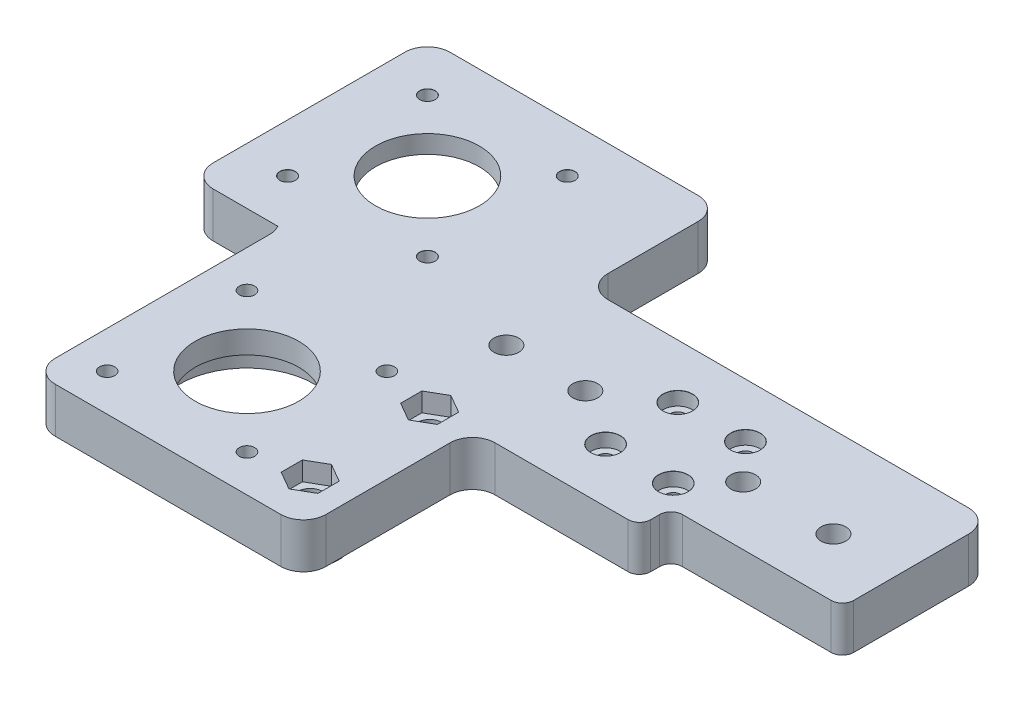
SolidWorks part; units mm, degrees
ref_plane "Front Plane" through (0, 0, 0) normal (0, 0, 1) x (1, 0, 0)
ref_plane "Top Plane" through (0, 0, 0) normal (0, 1, 0) x (1, 0, 0)
ref_plane "Right Plane" through (0, 0, 0) normal (1, 0, 0) x (0, 0, -1)
sketch "Sketch1" plane through (0, 0, 0) normal (0, 1, 0) x (1, 0, 0)
  line L0 (0, 0) -> (110, 0) construction
  line L1 (110, 0) -> (110, 20) construction
  line L2 (110, 20) -> (0, 20) construction
  line L3 (0, 20) -> (0, 0) construction
  line L4 (110, 30) -> (110, -10) construction
  line L5 (110, 30) -> (80, 30) construction
  line L6 (80, 30) -> (80, -10) construction
  line L7 (80, -10) -> (110, -10) construction
  line L8 (0, 67.5) -> (0, -47.5)
  line L16 (0, 67.5) -> (60, 67.5)
  line L18 (0, -47.5) -> (60, -47.5)
  line L19 (60, 67.5) -> (60, 30)
  line L22 (110, -10) -> (60, -10)
  line L23 (60, -10) -> (60, -47.5)
  line L24 (60, 30) -> (110, 30)
  line L25 (110, 30) -> (110, -10)
  point P8 (110, 10)
  point P13 (0, 10)
  dimension "D1" = 20
  dimension "D2" = 37.5
  dimension "D3" = 30
  dimension "D4" = 40
  dimension "D5" = 110
  dimension "D6" = 20
extrude "Boss-Extrude1" add sketch "Sketch1" along normal blind 10
fillet "Fillet1" radius 5 7 edges at (60, 5, -30) (110, 5, -30) (110, 5, 10) (0, 5, 47.5) (0, 5, -67.5) (60, 5, -67.5) (60, 5, 47.5)
sketch "Sketch3" plane through (0, 10, 0) normal (0, 1, 0) x (1, 0, 0)
  line L0 (5, -47.5) -> (55, -47.5) construction
  line L1 (0, 62.5) -> (0, -42.5) construction
  circle A0 centre (23.75, -23.75) radius 11.5
  dimension "D3" = 23
  dimension "D1" = 23.75
  dimension "D2" = 23.75
extrude "Cut-Extrude1" cut sketch "Sketch3" against normal blind 10
sketch "Sketch4" plane through (0, 0, 0) normal (0, -1, 0) x (1, 0, 0)
  line L1 (39.25, 39.25) -> (8.25, 39.25)
  line L2 (39.25, 39.25) -> (39.25, 8.25)
  line L3 (39.25, 8.25) -> (8.25, 8.25)
  line L4 (8.25, 39.25) -> (8.25, 8.25)
  line L5 (39.25, 39.25) -> (8.25, 8.25) construction
  line L6 (39.25, 8.25) -> (8.25, 39.25) construction
  point P0 (23.75, 23.75)
  dimension "D1" = 31
hole_wizard "CBORE for M3 SHCS1" positions "Sketch5" profile "Sketch6" counterbore size "M3" standard "ANSI Metric" end condition through all
sketch "Sketch5" plane through (0, 0, 0) normal (0, -1, 0) x (-1, 0, 0)
  point P0 (-39.25, -8.25)
  point P3 (-8.25, -39.25)
  point P6 (-8.25, -8.25)
  point P9 (-39.25, -39.25)
sketch "Sketch6" plane through (39.25, 0, 8.25) normal (1, 0, 0) x (0, 0, -1)
  line L0 (0, 0) -> (0, 10)
  line L1 (0, 10) -> (1.7, 10)
  line L3 (1.7, 10) -> (1.7, 3)
  line L4 (3.25, 3) -> (1.7, 3)
  line L5 (3.25, 3) -> (3.25, 0.025)
  line L6 (3.25, 0.025) -> (3.275, 0)
  line L7 (3.275, 0) -> (0, 0)
  line L8 (-3.25, 0.025) -> (-3.275, 0) construction
  line L11 (0, -6.35) -> (0, 107.95) construction
  dimension "Thru Hole Dia." = 3.4
  dimension "Thru Hole Depth" = 10
  dimension "C'Bore Dia." = 6.5
  dimension "C'Bore Depth" = 3
  dimension "Near C'Sink Dia." = 6.55
  dimension "Near C'Sink Angle" = 90
sketch "Sketch7" plane through (0, 10, 0) normal (0, 1, 0) x (1, 0, 0)
  line L1 (92.5, 18) -> (77.5, 18)
  line L2 (92.5, 18) -> (92.5, 2)
  line L3 (92.5, 2) -> (77.5, 2)
  line L4 (77.5, 18) -> (77.5, 2)
  line L5 (92.5, 18) -> (77.5, 2) construction
  line L6 (92.5, 2) -> (77.5, 18) construction
  line L7 (110, 10) -> (0, 10)
  line L8 (0, 67.5) -> (0, -47.5) construction
  line L10 (110, 30) -> (110, -10) construction
  point P0 (85, 10)
  dimension "D1" = 15
  dimension "D2" = 16
  dimension "D3" = 25
hole_wizard "CBORE for M3 SHCS2" positions "Sketch8" profile "Sketch9" counterbore size "M3" standard "ANSI Metric" end condition through all
sketch "Sketch8" plane through (0, 10, 0) normal (0, 1, 0) x (1, 0, 0)
  point P0 (77.5, 18)
  point P3 (92.5, 18)
  point P6 (92.5, 2)
  point P9 (77.5, 2)
sketch "Sketch9" plane through (77.5, 10, -18) normal (1, 0, 0) x (0, 0, 1)
  line L0 (0, 0) -> (0, 10)
  line L1 (0, 10) -> (1.7, 10)
  line L3 (1.7, 10) -> (1.7, 3)
  line L4 (3.25, 3) -> (1.7, 3)
  line L5 (3.25, 3) -> (3.25, 0.025)
  line L6 (3.25, 0.025) -> (3.275, 0)
  line L7 (3.275, 0) -> (0, 0)
  line L8 (-3.25, 0.025) -> (-3.275, 0) construction
  line L11 (0, -6.35) -> (0, 107.95) construction
  dimension "Thru Hole Dia." = 3.4
  dimension "Thru Hole Depth" = 10
  dimension "C'Bore Dia." = 6.5
  dimension "C'Bore Depth" = 3
  dimension "Near C'Sink Dia." = 6.55
  dimension "Near C'Sink Angle" = 90
sketch "Sketch10" plane through (0, 0, 0) normal (0, -1, 0) x (1, 0, 0)
  line L0 (110, -10) -> (0, -10) construction
  line L1 (110, 5) -> (110, -25) construction
  line L2 (0, -62.5) -> (0, 42.5) construction
  point P6 (100, -10)
  point P7 (30, -10)
  point P8 (47.5, -10)
  point P9 (65, -10)
  dimension "D1" = 30
  dimension "D2" = 17.5
  dimension "D3" = 17.5
  dimension "D4" = 10
hole_wizard "CBORE for M5 SHCS1" positions "Sketch13" profile "Sketch12" counterbore size "M5" standard "ANSI Metric" end condition through all
sketch "Sketch13" plane through (0, 0, 0) normal (0, -1, 0) x (-1, 0, 0)
  point P0 (-100, 10)
  point P3 (-65, 10)
  point P6 (-47.5, 10)
sketch "Sketch12" plane through (100, 0, -10) normal (1, 0, 0) x (0, 0, -1)
  line L0 (0, 0) -> (0, 10)
  line L1 (0, 10) -> (2.75, 10)
  line L3 (2.75, 10) -> (2.75, 5)
  line L4 (5, 5) -> (2.75, 5)
  line L5 (5, 5) -> (5, 0.025)
  line L6 (5, 0.025) -> (5.025, 0)
  line L7 (5.025, 0) -> (0, 0)
  line L8 (-5, 0.025) -> (-5.025, 0) construction
  line L11 (0, -6.35) -> (0, 107.95) construction
  dimension "Thru Hole Dia." = 5.5
  dimension "Thru Hole Depth" = 10
  dimension "C'Bore Dia." = 10
  dimension "C'Bore Depth" = 5
  dimension "Near C'Sink Dia." = 10.05
  dimension "Near C'Sink Angle" = 90
sketch "Sketch14" plane through (0, 10, 0) normal (0, 1, 0) x (1, 0, 0)
  line L0 (0, 10) -> (-17.5, 10)
  line L1 (0, 62.5) -> (0, -42.5) construction
  line L2 (-17.5, 10) -> (-17.5, 67.5)
  line L3 (-17.5, 67.5) -> (5, 67.5)
  line L4 (0, 62.5) -> (0, 10)
  arc A0 (5, 67.5) -> (0, 62.5) centre (5, 62.5) ccw construction
  arc A1 (5, 67.5) -> (0, 62.5) centre (5, 62.5) ccw
  dimension "D1" = 17.5
extrude "Boss-Extrude2" add sketch "Sketch14" against normal blind 10
sketch "Sketch15" plane through (0, 10, 0) normal (0, 1, 0) x (1, 0, 0)
  line L0 (-17.5, 67.5) -> (55, 67.5)
  line L1 (-17.5, 67.5) -> (-17.5, 57.5)
  line L2 (-17.5, 67.5) -> (-17.5, 10) construction
  line L3 (-17.5, 57.5) -> (60, 57.5)
  line L5 (60, 35) -> (60, 62.5) construction
  line L6 (60, 57.5) -> (60, 62.5)
  arc A2 (60, 62.5) -> (55, 67.5) centre (55, 62.5) ccw construction
  arc A3 (60, 62.5) -> (55, 67.5) centre (55, 62.5) ccw
  dimension "D1" = 10
extrude "Cut-Extrude2" cut sketch "Sketch15" against normal blind 10
fillet "Fillet2" radius 5 4 edges at (0, 5, -10) (60, 5, -57.5) (-17.5, 5, -57.5) (-17.5, 5, -10)
sketch "Sketch16" plane through (0, 10, 0) normal (0, 1, 0) x (1, 0, 0)
  line L0 (-12.5, 57.5) -> (55, 57.5) construction
  line L1 (-17.5, 52.5) -> (-17.5, 15) construction
  circle A0 centre (6.25, 33.75) radius 11.5
  dimension "D1" = 23
  dimension "D2" = 23.75
  dimension "D3" = 23.75
extrude "Cut-Extrude3" cut sketch "Sketch16" against normal through all
sketch "Sketch17" plane through (0, 10, 0) normal (0, 1, 0) x (1, 0, 0)
  line L1 (21.75, 49.25) -> (-9.25, 49.25)
  line L2 (21.75, 49.25) -> (21.75, 18.25)
  line L3 (21.75, 18.25) -> (-9.25, 18.25)
  line L4 (-9.25, 49.25) -> (-9.25, 18.25)
  line L5 (21.75, 49.25) -> (-9.25, 18.25) construction
  line L6 (21.75, 18.25) -> (-9.25, 49.25) construction
  point P0 (6.25, 33.75)
  dimension "D1" = 31
hole_wizard "M3 Clearance Hole1" positions "Sketch18" profile "Sketch19" hole size "M3" standard "ANSI Metric" end condition through all
sketch "Sketch18" plane through (0, 10, 0) normal (0, 1, 0) x (1, 0, 0)
  point P0 (-9.25, 49.25)
  point P3 (21.75, 49.25)
  point P6 (21.75, 18.25)
  point P9 (-9.25, 18.25)
sketch "Sketch19" plane through (-9.25, 10, -49.25) normal (1, 0, 0) x (0, 0, 1)
  line L0 (0, 0) -> (0, 10)
  line L1 (0, 10) -> (1.7, 10)
  line L2 (1.7, 10) -> (1.7, 0.025)
  line L3 (1.7, 0.025) -> (1.725, 0)
  line L5 (1.725, 0) -> (0, 0)
  line L6 (-1.7, 0.025) -> (-1.725, 0) construction
  line L11 (0, -6.35) -> (0, 107.95) construction
  dimension "Thru Hole Dia." = 3.4
  dimension "Thru Hole Depth" = 10
  dimension "Near C'Sink Dia." = 3.45
  dimension "Near C'Sink Angle" = 90
sketch "Sketch20" plane through (0, 10, 0) normal (0, 1, 0) x (1, 0, 0)
  line L0 (23.75, -23.75) -> (60, -23.75) construction
  line L1 (60, -42.5) -> (60, -10) construction
  line L2 (51, -10.51) -> (51, -36.99) construction
  line L4 (55.075, -8.1573) -> (51, -5.8046)
  line L5 (51, -5.8046) -> (46.925, -8.1573)
  line L6 (46.925, -8.1573) -> (46.925, -12.8627)
  line L7 (46.925, -12.8627) -> (51, -15.2154)
  line L8 (51, -15.2154) -> (55.075, -12.8627)
  line L9 (55.075, -12.8627) -> (55.075, -8.1573)
  line L10 (51, -32.2846) -> (46.925, -34.6373)
  line L11 (46.925, -34.6373) -> (46.925, -39.3427)
  line L12 (46.925, -39.3427) -> (51, -41.6954)
  line L13 (51, -41.6954) -> (55.075, -39.3427)
  line L14 (55.075, -39.3427) -> (55.075, -34.6373)
  line L15 (55.075, -34.6373) -> (51, -32.2846)
  line L18 (0, 5) -> (0, -42.5) construction
  circle A0 centre (51, -10.51) radius 4.075 construction
  circle A1 centre (51, -36.99) radius 4.075 construction
  point P8 (51, -23.75)
  point P25 (51, -36.99)
  point P26 (51, -10.51)
  dimension "D1" = 26.48
  dimension "D2" = 9
  dimension "D3" = 8.15
extrude "Cut-Extrude4" cut sketch "Sketch20" against normal blind 4.2
hole_wizard "M5 Clearance Hole1" positions "Sketch22" profile "Sketch23" hole size "M5" standard "ANSI Metric" end condition through all
sketch "Sketch22" plane through (0, 10, 0) normal (0, 1, 0) x (1, 0, 0)
  point P0 (51, -10.51)
  point P3 (51, -36.99)
sketch "Sketch23" plane through (51, 10, 10.51) normal (1, 0, 0) x (0, 0, 1)
  line L0 (0, 0) -> (0, 10)
  line L1 (0, 10) -> (2.75, 10)
  line L2 (2.75, 10) -> (2.75, 0.025)
  line L3 (2.75, 0.025) -> (2.775, 0)
  line L5 (2.775, 0) -> (0, 0)
  line L6 (-2.75, 0.025) -> (-2.775, 0) construction
  line L11 (0, -6.35) -> (0, 107.95) construction
  dimension "Thru Hole Dia." = 5.5
  dimension "Thru Hole Depth" = 10
  dimension "Near C'Sink Dia." = 5.55
  dimension "Near C'Sink Angle" = 90
sketch "Sketch25" plane through (0, 0, 0) normal (0, -1, 0) x (1, 0, 0)
  circle A0 centre (23.75, 23.75) radius 15
  dimension "D1" = 30
extrude "Cut-Extrude6" cut sketch "Sketch25" against normal blind 5
sketch "Sketch26" plane through (0, 0, 0) normal (0, -1, 0) x (1, 0, 0)
  circle A0 centre (51, 36.99) radius 6.25
  circle A1 centre (51, 36.99) radius 2.75 construction
  circle A2 centre (51, 36.99) radius 2.75
  circle A3 centre (51, 10.51) radius 6.25
  circle A4 centre (51, 10.51) radius 2.75 construction
  circle A5 centre (51, 10.51) radius 2.75
  dimension "D1" = 12.5
extrude "Boss-Extrude3" add sketch "Sketch26" along normal blind 2.9
sketch "Sketch27" plane through (0, 10, 0) normal (0, 1, 0) x (1, 0, 0)
  line L0 (65, 30) -> (45, 30)
  line L1 (45, 30) -> (45, 57.5)
  line L2 (-12.5, 57.5) -> (55, 57.5) construction
  line L3 (45, 57.5) -> (55, 57.5)
  line L4 (60, 35) -> (60, 52.5) construction
  line L5 (60, 35) -> (60, 52.5)
  arc A0 (60, 35) -> (65, 30) centre (65, 35) ccw construction
  arc A1 (60, 52.5) -> (55, 57.5) centre (55, 52.5) ccw construction
  arc A2 (60, 35) -> (65, 30) centre (65, 35) ccw
  arc A3 (60, 52.5) -> (55, 57.5) centre (55, 52.5) ccw
  dimension "D1" = 15
extrude "Cut-Extrude7" cut sketch "Sketch27" against normal blind 10
fillet "Fillet3" radius 5 3 edges at (45, 5, -57.5) (45, 5, -30) (60, 5, 10)
sketch "Sketch31" plane through (0, 10, 0) normal (0, 1, 0) x (1, 0, 0)
  line L0 (-10.5429, 54.2071) -> (-14.2071, 50.5429) construction
  line L1 (22.3358, 54.5) -> (-9.8358, 54.5) construction
  line L2 (26.7071, 50.5429) -> (23.0429, 54.2071) construction
  line L3 (27, 17.6642) -> (27, 49.8358) construction
  line L4 (23.0429, 13.2929) -> (26.7071, 16.9571) construction
  line L5 (-9.8358, 13) -> (22.3358, 13) construction
  line L6 (-14.2071, 16.9571) -> (-10.5429, 13.2929) construction
  line L7 (-14.5, 49.8358) -> (-14.5, 17.6642) construction
  line L8 (-10.5429, 54.2071) -> (-14.2071, 50.5429) construction
  line L9 (22.3358, 54.5) -> (-9.8358, 54.5) construction
  line L10 (-15.5, 49.8358) -> (-15.5, 17.6642)
  line L11 (-14.9142, 16.25) -> (-11.25, 12.5858)
  line L12 (-9.8358, 12) -> (22.3358, 12)
  line L13 (23.75, 12.5858) -> (27.4142, 16.25)
  line L14 (28, 17.6642) -> (28, 49.8358)
  line L15 (27.4142, 51.25) -> (23.75, 54.9142)
  line L16 (22.3358, 55.5) -> (-9.8358, 55.5)
  line L17 (-11.25, 54.9142) -> (-14.9142, 51.25)
  line L30 (26.7071, 50.5429) -> (23.0429, 54.2071) construction
  line L31 (27, 17.6642) -> (27, 49.8358) construction
  line L32 (23.0429, 13.2929) -> (26.7071, 16.9571) construction
  line L33 (-9.8358, 13) -> (22.3358, 13) construction
  line L34 (-14.2071, 16.9571) -> (-10.5429, 13.2929) construction
  line L35 (-14.5, 49.8358) -> (-14.5, 17.6642) construction
  arc A0 (-14.2071, 50.5429) -> (-14.5, 49.8358) centre (-13.5, 49.8358) ccw construction
  arc A1 (-9.8358, 54.5) -> (-10.5429, 54.2071) centre (-9.8358, 53.5) ccw construction
  arc A2 (23.0429, 54.2071) -> (22.3358, 54.5) centre (22.3358, 53.5) ccw construction
  arc A3 (27, 49.8358) -> (26.7071, 50.5429) centre (26, 49.8358) ccw construction
  arc A4 (26.7071, 16.9571) -> (27, 17.6642) centre (26, 17.6642) ccw construction
  arc A5 (22.3358, 13) -> (23.0429, 13.2929) centre (22.3358, 14) ccw construction
  arc A6 (-10.5429, 13.2929) -> (-9.8358, 13) centre (-9.8358, 14) ccw construction
  arc A7 (-14.5, 17.6642) -> (-14.2071, 16.9571) centre (-13.5, 17.6642) ccw construction
  arc A8 (-14.2071, 50.5429) -> (-14.5, 49.8358) centre (-13.5, 49.8358) ccw construction
  arc A9 (-14.9142, 51.25) -> (-15.5, 49.8358) centre (-13.5, 49.8358) ccw
  arc A10 (-15.5, 17.6642) -> (-14.9142, 16.25) centre (-13.5, 17.6642) ccw
  arc A11 (-11.25, 12.5858) -> (-9.8358, 12) centre (-9.8358, 14) ccw
  arc A12 (22.3358, 12) -> (23.75, 12.5858) centre (22.3358, 14) ccw
  arc A14 (27.4142, 16.25) -> (28, 17.6642) centre (26, 17.6642) ccw
  arc A15 (28, 49.8358) -> (27.4142, 51.25) centre (26, 49.8358) ccw
  arc A17 (23.75, 54.9142) -> (22.3358, 55.5) centre (22.3358, 53.5) ccw
  arc A27 (-9.8358, 54.5) -> (-10.5429, 54.2071) centre (-9.8358, 53.5) ccw construction
  arc A28 (23.0429, 54.2071) -> (22.3358, 54.5) centre (22.3358, 53.5) ccw construction
  arc A29 (27, 49.8358) -> (26.7071, 50.5429) centre (26, 49.8358) ccw construction
  arc A30 (26.7071, 16.9571) -> (27, 17.6642) centre (26, 17.6642) ccw construction
  arc A31 (22.3358, 13) -> (23.0429, 13.2929) centre (22.3358, 14) ccw construction
  arc A32 (-10.5429, 13.2929) -> (-9.8358, 13) centre (-9.8358, 14) ccw construction
  arc A33 (-14.5, 17.6642) -> (-14.2071, 16.9571) centre (-13.5, 17.6642) ccw construction
  arc A34 (-9.8358, 55.5) -> (-11.25, 54.9142) centre (-9.8358, 53.5) ccw
  dimension "D1" = 1
extrude "Cut-Extrude9" cut sketch "Sketch31" along normal blind 6 from surface starting at face at (51, 0, 43.24)
sketch "Sketch32" plane through (0, 0, 0) normal (0, -1, 0) x (1, 0, 0)
  line L1 (-20, -7.5) -> (-20, -60)
  line L2 (45, -52.5) -> (45, -60)
  line L3 (45, -60) -> (-20, -60)
  line L4 (-12.5, -57.5) -> (40, -57.5) construction
  line L5 (-17.5, -52.5) -> (-17.5, -15) construction
  line L6 (-12.5, -57.5) -> (40, -57.5)
  line L7 (-17.5, -52.5) -> (-17.5, -15)
  line L8 (-0.6699, -7.5) -> (-20, -7.5)
  line L10 (-12.5, -10) -> (-5, -10) construction
  line L11 (-12.5, -10) -> (-5, -10)
  arc A0 (40, -57.5) -> (45, -52.5) centre (40, -52.5) ccw construction
  arc A1 (-17.5, -52.5) -> (-12.5, -57.5) centre (-12.5, -52.5) ccw construction
  arc A2 (-12.5, -10) -> (-17.5, -15) centre (-12.5, -15) ccw construction
  arc A3 (40, -57.5) -> (45, -52.5) centre (40, -52.5) ccw
  arc A4 (-17.5, -52.5) -> (-12.5, -57.5) centre (-12.5, -52.5) ccw
  arc A5 (-12.5, -10) -> (-17.5, -15) centre (-12.5, -15) ccw
  arc A7 (-5, -10) -> (0, -5) centre (-5, -5) ccw construction
  arc A8 (-5, -10) -> (-0.6699, -7.5) centre (-5, -5) ccw
  dimension "D1" = 7.5
  dimension "D2" = 7.5
  dimension "D3" = 7.5
extrude "Boss-Extrude5" add sketch "Sketch32" against normal up to surface (10 mm away) up to face at (39.5, 10, -8)
fillet "Fillet4" radius 5 3 edges at (45, 5, -60) (-20, 5, -60) (-20, 5, -7.5)
sketch "Sketch33" plane through (0, 0, 0) normal (0, -1, 0) x (1, 0, 0)
  line L0 (105, -30) -> (135, -30)
  line L1 (105, 10) -> (135, 10)
  line L2 (135, 10) -> (135, -30)
  line L3 (110, 5) -> (110, -25) construction
  line L4 (110, 5) -> (110, -25)
  arc A0 (110, 5) -> (105, 10) centre (105, 5) ccw construction
  arc A1 (105, -30) -> (110, -25) centre (105, -25) ccw construction
  arc A2 (110, 5) -> (105, 10) centre (105, 5) ccw
  arc A3 (105, -30) -> (110, -25) centre (105, -25) ccw
  dimension "D1" = 25
extrude "Boss-Extrude6" add sketch "Sketch33" against normal up to surface (10 mm away) up to face at (39.173, 10, -8.0754)
sketch "Sketch34" plane through (0, 0, 0) normal (0, -1, 0) x (1, 0, 0)
  line L0 (135, -30) -> (135, 10) construction
  line L1 (135, -10) -> (-19.3472, -10.0297) construction
  arc A1 (-15, -7.5) -> (-20, -12.5) centre (-15, -12.5) ccw construction
  circle A2 centre (100, -10) radius 2.75 construction
  point P0 (120, -10.0029)
  dimension "D1" = 20
hole_wizard "CBORE for M5 SHCS2" positions "Sketch35" profile "Sketch36" counterbore size "M5" standard "ANSI Metric" end condition through all
sketch "Sketch35" plane through (0, 0, 0) normal (0, -1, 0) x (-1, 0, 0)
  point P0 (-120, 10.0029)
sketch "Sketch36" plane through (120, 0, -10.0029) normal (1, 0, 0) x (0, 0, -1)
  line L0 (0, 0) -> (0, 10)
  line L1 (0, 10) -> (2.75, 10)
  line L3 (2.75, 10) -> (2.75, 5)
  line L4 (5, 5) -> (2.75, 5)
  line L5 (5, 5) -> (5, 0.021)
  line L6 (5, 0.021) -> (5.025, 0)
  line L7 (5.025, 0) -> (0, 0)
  line L8 (-5, 0.021) -> (-5.025, 0) construction
  line L11 (0, -6.35) -> (0, 107.95) construction
  dimension "Thru Hole Dia." = 5.5
  dimension "Thru Hole Depth" = 10
  dimension "C'Bore Dia." = 10
  dimension "C'Bore Depth" = 5
  dimension "Near C'Sink Dia." = 10.05
  dimension "Near C'Sink Angle" = 100
fillet "Fillet5" radius 5 2 edges at (135, 5, -30) (135, 5, 10)
sketch "Sketch38" plane through (0, 0, 0) normal (0, -1, 0) x (1, 0, 0)
  line L0 (130, -30) -> (50, -30) construction
  line L1 (68, -30) -> (74, -30)
  line L2 (68, -30) -> (68, -13.5)
  line L3 (68, -13.5) -> (74, -13.5)
  line L4 (74, -30) -> (74, -13.5)
  line L5 (45, -55) -> (45, -35) construction
  line L7 (96, -24) -> (112.5, -24)
  line L8 (96, -24) -> (96, -30)
  line L9 (96, -30) -> (112.5, -30)
  line L10 (112.5, -24) -> (112.5, -30)
  line L11 (135, -25) -> (135, 5) construction
  dimension "D1" = 6
  dimension "D2" = 29
  dimension "D3" = 16.5
  dimension "D4" = 39
  dimension "D5" = 16.5
  dimension "D6" = 6
extrude "Boss-Extrude7" add sketch "Sketch38" along normal blind 21
fillet "Fillet6" radius 1 8 edges at (74, -10.5, -13.5) (68, -10.5, -13.5) (68, -10.5, -30) (74, -10.5, -30) (96, -10.5, -30) (112.5, -10.5, -30) (112.5, -10.5, -24) (96, -10.5, -24)
sketch "Sketch39" plane through (68, 0, 0) normal (-1, 0, 0) x (0, 0, 1)
  circle A0 centre (-19.79, -6.5) radius 1.25 construction
  circle A1 centre (-19.79, -16) radius 1.25 construction
  circle A2 centre (-19.79, -6.5) radius 1.25 construction
  circle A3 centre (-19.79, -16) radius 1.25 construction
  circle A4 centre (-19.79, -6.5) radius 1.1
  circle A5 centre (-19.79, -16) radius 1.1
  dimension "D1" = 0.15
extrude "Cut-Extrude10" cut sketch "Sketch39" against normal blind 3
sketch "Sketch42" plane through (0, -21, 0) normal (0, -1, 0) x (1, 0, 0)
  line L4 (96, -25) -> (96, -29)
  line L5 (97, -30) -> (111.5, -30)
  line L6 (112.5, -29) -> (112.5, -25)
  line L7 (111.5, -24) -> (97, -24)
  line L8 (96, -25) -> (96, -29)
  line L9 (97, -30) -> (111.5, -30)
  line L10 (112.5, -29) -> (112.5, -25)
  line L11 (111.5, -24) -> (97, -24)
  arc A4 (96, -29) -> (97, -30) centre (97, -29) ccw
  arc A5 (111.5, -30) -> (112.5, -29) centre (111.5, -29) ccw
  arc A6 (112.5, -25) -> (111.5, -24) centre (111.5, -25) ccw
  arc A7 (97, -24) -> (96, -25) centre (97, -25) ccw
  arc A8 (96, -29) -> (97, -30) centre (97, -29) ccw
  arc A9 (111.5, -30) -> (112.5, -29) centre (111.5, -29) ccw
  arc A10 (112.5, -25) -> (111.5, -24) centre (111.5, -25) ccw
  arc A11 (97, -24) -> (96, -25) centre (97, -25) ccw
  dimension "D1" = 0
extrude "Cut-Extrude11" cut sketch "Sketch42" against normal blind 14
sketch "Sketch43" plane through (0, 0, -30) normal (0, 0, -1) x (-1, 0, 0)
  circle A0 centre (-98.9, -1.5) radius 1.25 construction
  circle A1 centre (-98.9, 8) radius 1.25 construction
  circle A2 centre (-98.9, -1.5) radius 1.25 construction
  circle A3 centre (-98.9, 8) radius 1.25 construction
  circle A4 centre (-98.9, 8) radius 1.15
  circle A5 centre (-98.9, -1.5) radius 1.15
  dimension "D1" = 0.1
extrude "Cut-Extrude12" cut sketch "Sketch43" against normal blind 3
sketch "Sketch44" plane through (0, 10, 0) normal (0, 1, 0) x (1, 0, 0)
  line L0 (130, -10) -> (97, -10)
  line L1 (65, -10) -> (130, -10) construction
  line L2 (97, -10) -> (97, -3)
  line L3 (97, -3) -> (135, -3)
  line L4 (135, 25) -> (135, -5) construction
  line L5 (135, -3) -> (135, -5)
  arc A0 (130, -10) -> (135, -5) centre (130, -5) ccw construction
  arc A1 (130, -10) -> (135, -5) centre (130, -5) ccw
  dimension "D1" = 7
  dimension "D2" = 38
extrude "Cut-Extrude13" cut sketch "Sketch44" against normal through all
fillet "Fillet7" radius 2.5 3 edges at (135, 5, 3) (97, 5, 10) (97, 5, 3)
